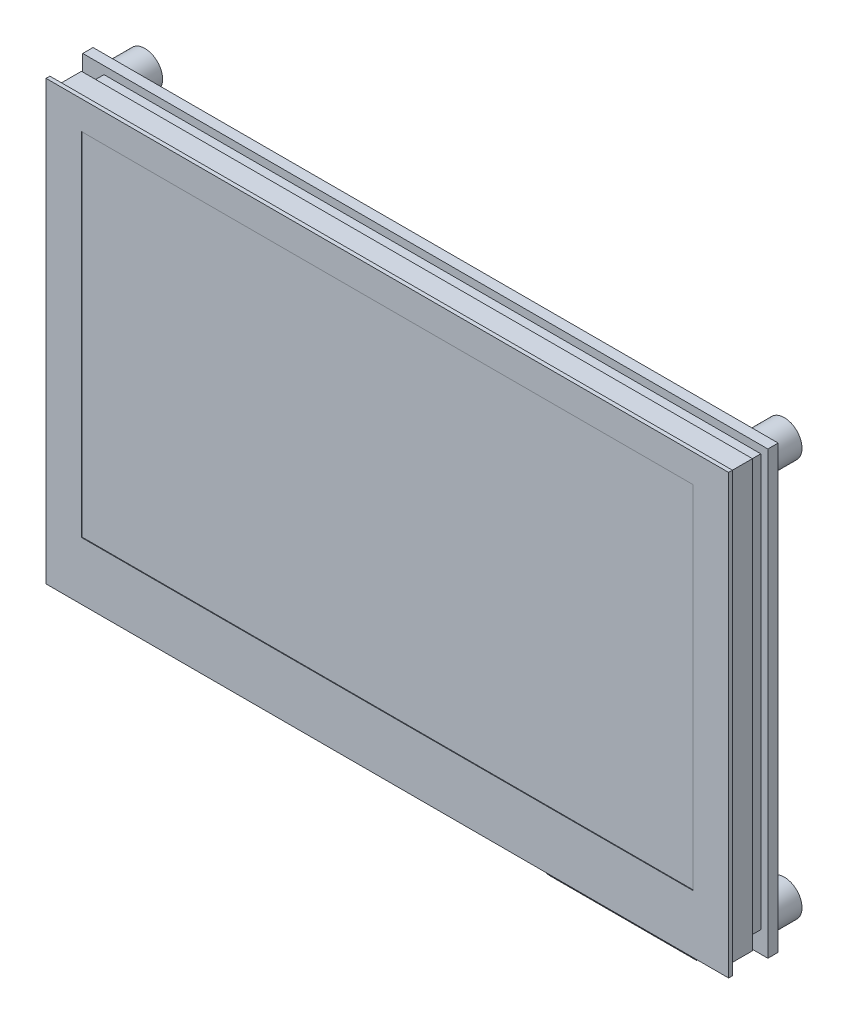
SolidWorks part; units mm, degrees
ref_plane "Front" through (0, 0, 0) normal (0, 0, 1) x (1, 0, 0)
ref_plane "Top" through (0, 0, 0) normal (0, 1, 0) x (1, 0, 0)
ref_plane "Right" through (0, 0, 0) normal (1, 0, 0) x (0, 0, -1)
sketch "Sketch1" plane through (0, 0, 0) normal (0, 0, 1) x (1, 0, 0)
  line L1 (-53, 34) -> (53, 34)
  line L2 (-53, 34) -> (-53, -34)
  line L3 (-53, -34) -> (53, -34)
  line L4 (53, 34) -> (53, -34)
  line L5 (-53, 34) -> (53, -34) construction
  line L6 (-53, -34) -> (53, 34) construction
  point P0 (0, 0)
  dimension "D1" = 106
  dimension "D2" = 68
extrude "Boss-Extrude1" add sketch "Sketch1" along normal blind 0.6
sketch "Sketch2" plane through (0, 0, 0.6) normal (0, 0, 1) x (1, 0, 0)
  line L0 (53, 34) -> (-53, 34) construction
  line L1 (-47.5, 29.6) -> (47.5, 29.6)
  line L2 (-47.5, 29.6) -> (-47.5, -25)
  line L3 (-47.5, -25) -> (47.5, -25)
  line L4 (47.5, 29.6) -> (47.5, -25)
  line L5 (-53, 34) -> (-53, -34) construction
  line L6 (53, -34) -> (53, 34) construction
  line L7 (-53, -34) -> (53, -34) construction
  dimension "D1" = 4.4
  dimension "D2" = 5.5
  dimension "D3" = 5.5
  dimension "D4" = 9
extrude "Cut-Extrude1" cut sketch "Sketch2" against normal blind 0.1 contours L2 L1 L4 L3
sketch "Sketch4" plane through (0, 0, 0) normal (0, 0, -1) x (-1, 0, 0)
  line L0 (-53, 34) -> (53, 34) construction
  line L1 (-52.1, 33.1) -> (52.1, 33.1)
  line L2 (-52.1, 33.1) -> (-52.1, -33.1)
  line L3 (-52.1, -33.1) -> (52.1, -33.1)
  line L4 (52.1, 33.1) -> (52.1, -33.1)
  line L5 (-52.1, 33.1) -> (52.1, -33.1) construction
  line L6 (-52.1, -33.1) -> (52.1, 33.1) construction
  line L7 (-53, -34) -> (-53, 34) construction
  point P0 (0, 0)
  dimension "D1" = 0.9
  dimension "D2" = 0.9
extrude "Boss-Extrude2" add sketch "Sketch4" along normal blind 4
sketch "Sketch5" plane through (0, 0, -4) normal (0, 0, -1) x (-1, 0, 0)
  line L0 (-53, 34) -> (53, 34) construction
  line L1 (-51, 32) -> (51, 32)
  line L2 (-51, 32) -> (-51, -32)
  line L3 (-51, -32) -> (51, -32)
  line L4 (51, 32) -> (51, -32)
  line L5 (-51, 32) -> (51, -32) construction
  line L6 (-51, -32) -> (51, 32) construction
  line L7 (-53, -34) -> (-53, 34) construction
  point P0 (0, 0)
  dimension "D1" = 2
  dimension "D2" = 2
extrude "Boss-Extrude3" add sketch "Sketch5" along normal blind 2.4
sketch "Sketch6" plane through (0, 0, -6.4) normal (0, 0, -1) x (-1, 0, 0)
  line L0 (53, -34) -> (-53, -34) construction
  line L1 (-52.1, 33.2) -> (54.3, 33.2)
  line L2 (-52.1, 33.2) -> (-52.1, -35.3)
  line L3 (-52.1, -35.3) -> (54.3, -35.3)
  line L4 (54.3, 33.2) -> (54.3, -35.3)
  line L5 (-53, 34) -> (53, 34) construction
  line L6 (53, 34) -> (53, -34) construction
  line L7 (-53, -34) -> (-53, 34) construction
  point P12 (-52.1, -1.05)
  dimension "D1" = 1.3
  dimension "D2" = 0.8
  dimension "D3" = 1.3
  dimension "D4" = 0.9
extrude "Boss-Extrude4" add sketch "Sketch6" along normal blind 1.6
sketch "Sketch7" plane through (0, -33.1, 0) normal (0, -1, 0) x (1, 0, 0)
  line L0 (47.5, 0) -> (42.5, -5)
  line L1 (52.1, 0) -> (-52.1, 0) construction
  line L2 (42.5, -5) -> (28.5, -5)
  line L3 (28.5, -5) -> (23.5, 0)
  line L4 (23.5, 0) -> (47.5, 0)
  line L9 (53, 0.6) -> (53, 0) construction
  dimension "D1" = 45
  dimension "D2" = 24
  dimension "D3" = 14
  dimension "D4" = 5.5
extrude "Boss-Extrude5" add sketch "Sketch7" along normal blind 2.8 and the other way up to surface (1.1 mm away) other way up to face at (0, -32, -5.2)
fillet "Fillet1" radius 2 2 edges at (35.5, -35.9, 0) (35.5, -35.9, -5)
sketch "Sketch8" plane through (52.1, 0, 0) normal (1, 0, 0) x (0, 0, -1)
  line L0 (4, -33.1) -> (0, -33.1) construction
  line L1 (4.8256, -32.0158) -> (4, -32.0158)
  line L2 (4, 33.1) -> (4, -33.1) construction
  line L3 (4, -32.0158) -> (4, -33.1)
  line L4 (4, -33.1) -> (0.2556, -33.1)
  spline S0 degree 3 poles (0.2556, -33.1) (-0.1006, -35.3354) (4.5865, -36.5966) (4.9676, -32.9168) (4.8256, -32.0158) knots 0 0 0 0 0.60932 1 1 1 1
extrude "Cut-Extrude2" cut sketch "Sketch8" against normal up to surface (24.6 mm away) up to face at (26.379, -33.8392, -2.879)
sketch "Sketch9" plane through (0, 0, -8) normal (0, 0, -1) x (-1, 0, 0)
  line L0 (-52.1, 33.2) -> (-52.1, -35.3) construction
  line L1 (54.3, -35.3) -> (54.3, 33.2) construction
  line L2 (54.3, 33.2) -> (-52.1, 33.2) construction
  line L3 (-52.1, -35.3) -> (54.3, -35.3) construction
  circle A0 centre (-48.55, 29.85) radius 2.75
  circle A1 centre (-48.55, -31.95) radius 2.75
  circle A2 centre (50.75, 29.85) radius 2.75
  circle A3 centre (50.75, -31.95) radius 2.75
  circle A4 centre (-26.25, 23.6) radius 2.75
  circle A5 centre (-26.25, -25.7) radius 2.75
  circle A6 centre (31.65, 23.6) radius 2.75
  circle A7 centre (31.65, -25.7) radius 2.75
  dimension "D1" = 5.5
  dimension "D2" = 5.5
  dimension "D3" = 5.5
  dimension "D4" = 5.5
  dimension "D7" = 3.55
  dimension "D11" = 5.5
  dimension "D12" = 5.5
  dimension "D13" = 5.5
  dimension "D14" = 5.5
  dimension "D15" = 57.9
  dimension "D5" = 99.3
  dimension "D6" = 61.8
  dimension "D8" = 3.55
  dimension "D9" = 3.35
  dimension "D10" = 3.35
  dimension "D16" = 49.3
  dimension "D17" = 22.3
  dimension "D18" = 6.25
  dimension "D19" = 6.25
  dimension "D20" = 19.1
extrude "Boss-Extrude6" add sketch "Sketch9" along normal blind 4.5
sketch "Sketch10" plane through (0, 0, -12.5) normal (0, 0, -1) x (-1, 0, 0)
  circle A0 centre (-48.55, 29.85) radius 1.25
  circle A1 centre (-26.25, 23.6) radius 1.25
  circle A2 centre (31.65, 23.6) radius 1.25
  circle A3 centre (50.75, 29.85) radius 1.25
  circle A4 centre (-26.25, -25.7) radius 1.25
  circle A5 centre (-48.55, -31.95) radius 1.25
  circle A6 centre (50.75, -31.95) radius 1.25
  circle A7 centre (31.65, -25.7) radius 1.25
  dimension "D1" = 2.5
  dimension "D2" = 2.5
  dimension "D3" = 2.5
  dimension "D4" = 2.5
  dimension "D5" = 2.5
  dimension "D6" = 2.5
  dimension "D7" = 2.5
  dimension "D8" = 2.5
extrude "Cut-Extrude3" cut sketch "Sketch10" against normal up to surface (6.1 mm away) up to face at (-1.1, -1.05, -6.4)
sketch "Sketch11" plane through (0, 0, -8) normal (0, 0, -1) x (-1, 0, 0)
  line L0 (54.3, 33.2) -> (-52.1, 33.2) construction
  line L1 (49.5, -12.05) -> (52, -12.05)
  line L2 (49.5, -12.05) -> (49.5, 9.95)
  line L3 (49.5, 9.95) -> (52, 9.95)
  line L4 (52, -12.05) -> (52, 9.95)
  line L5 (49.5, -12.05) -> (52, 9.95) construction
  line L6 (49.5, 9.95) -> (52, -12.05) construction
  line L7 (-52.1, -35.3) -> (54.3, -35.3) construction
  line L8 (54.3, -35.3) -> (54.3, 33.2) construction
  point P0 (50.75, -1.05)
  dimension "D1" = 22
  dimension "D2" = 2.5
  dimension "D3" = 23.25
  dimension "D4" = 23.25
  dimension "D5" = 2.3
extrude "Boss-Extrude7" add sketch "Sketch11" along normal blind 5.6
sketch "Sketch12" plane through (0, 0, -8) normal (0, 0, -1) x (-1, 0, 0)
  line L0 (54.3, -35.3) -> (54.3, 33.2) construction
  line L1 (13.4, 10.4) -> (36.9, 10.4)
  line L2 (13.4, 10.4) -> (13.4, 4.4)
  line L3 (13.4, 4.4) -> (36.9, 4.4)
  line L4 (36.9, 10.4) -> (36.9, 4.4)
  line L5 (13.4, 10.4) -> (36.9, 4.4) construction
  line L6 (13.4, 4.4) -> (36.9, 10.4) construction
  line L7 (54.3, 33.2) -> (-52.1, 33.2) construction
  line L8 (-52.1, 33.2) -> (-52.1, -35.3) construction
  line L9 (-35.9, -9.3) -> (-29.4, -9.3)
  line L10 (-35.9, -9.3) -> (-35.9, -15.3)
  line L11 (-35.9, -15.3) -> (-29.4, -15.3)
  line L12 (-29.4, -9.3) -> (-29.4, -15.3)
  line L13 (-35.9, -9.3) -> (-29.4, -15.3) construction
  line L14 (-35.9, -15.3) -> (-29.4, -9.3) construction
  line L15 (-52.1, -35.3) -> (54.3, -35.3) construction
  point P0 (25.15, 7.4)
  point P9 (-32.65, -12.3)
  point P14 (-35.9, -12.3)
  dimension "D1" = 23.5
  dimension "D2" = 6
  dimension "D3" = 17.4
  dimension "D4" = 22.8
  dimension "D5" = 6.5
  dimension "D6" = 6
  dimension "D7" = 16.2
  dimension "D8" = 20
extrude "Boss-Extrude8" add sketch "Sketch12" along normal blind 3
